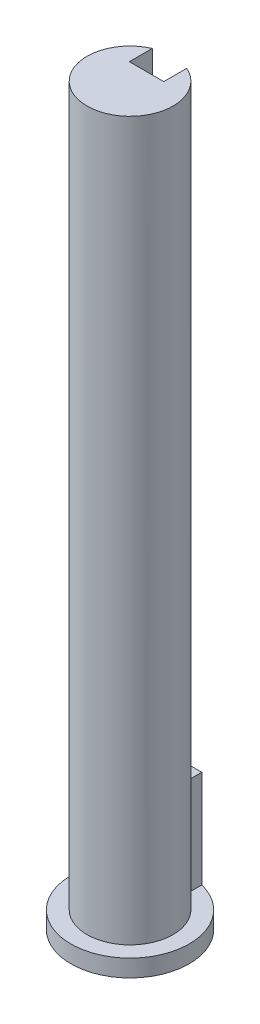
SolidWorks part; units mm, degrees
ref_plane "정면" through (0, 0, 0) normal (0, 0, 1) x (1, 0, 0)
ref_plane "윗면" through (0, 0, 0) normal (0, 1, 0) x (1, 0, 0)
ref_plane "우측면" through (0, 0, 0) normal (1, 0, 0) x (0, 0, -1)
sketch "스케치1" plane through (0, 0, 0) normal (0, 1, 0) x (1, 0, 0)
  line L0 (-1, 2.8284) -> (-1, 4)
  line L1 (-1, 4) -> (1, 4)
  line L2 (1, 4) -> (1, 2.8284)
  circle A0 centre (0, 0) radius 3
  dimension "D1" = 6
  dimension "D2" = 4
  dimension "D3" = 1
  dimension "D4" = 2
extrude "보스-돌출2" add sketch "스케치1" along normal blind 50 contours A0 region at (0, 0, 0)
extrude "보스-돌출3" add sketch "스케치1<3>" along normal blind 6.8 contours A0 L2 L1 L0 region at (0, 0, -3.4705)
sketch "스케치1<3>" plane through (0, 0, 0) normal (0, 1, 0) x (1, 0, 0) same geometry as "스케치1"
sketch "스케치2" plane through (0, 50, 0) normal (0, 1, 0) x (1, 0, 0)
  line L5 (-1.2, 1.1495) -> (1.2, 1.1495)
  line L6 (1.2, 1.1495) -> (1.2, 2.7495)
  line L7 (-1.2, 1.1495) -> (-1.2, 2.7495)
  line L8 (0, 0) -> (0, 1.1495) construction
  line L9 (-1.2, 2.7495) -> (0, 4.828)
  line L10 (0, 4.828) -> (1.2, 2.7495)
  circle A0 centre (0, 0) radius 3 construction
  dimension "D1" = 1.6
  dimension "D5" = 2.4
  dimension "D6" = 60
  dimension "D7" = 150
extrude "컷-돌출1" cut sketch "스케치2" against normal blind 37.2
sketch "스케치3" plane through (0, 0, 0) normal (0, -1, 0) x (1, 0, 0)
  circle A0 centre (0, 0) radius 4.1231
extrude "보스-돌출4" add sketch "스케치3" along normal blind 1.2
